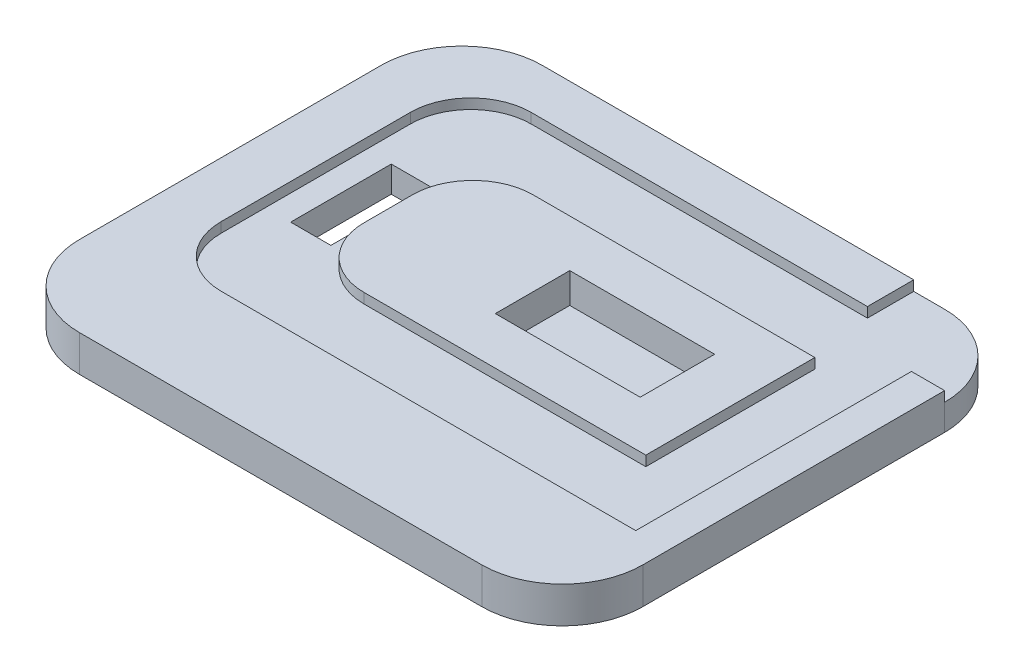
SolidWorks part; units mm, degrees
ref_plane "Front" through (0, 0, 0) normal (0, 0, 1) x (1, 0, 0)
ref_plane "Top" through (0, 0, 0) normal (0, 1, 0) x (1, 0, 0)
ref_plane "Right" through (0, 0, 0) normal (1, 0, 0) x (0, 0, -1)
sketch "Sketch2" plane through (0, 0, 0) normal (0, 1, 0) x (1, 0, 0)
  line L1 (-80, 50) -> (60, 50)
  line L2 (-80, 50) -> (-80, -65)
  line L3 (-80, -65) -> (60, -65)
  line L4 (60, 50) -> (60, -65)
  dimension "D1" = 140
  dimension "D2" = 115
  dimension "D3" = 65
  dimension "D4" = 80
extrude "Boss-Extrude1" add sketch "Sketch2" against normal blind 9 contours L3 L4 L1 L2
sketch "Sketch3" plane through (0, 0, 0) normal (0, 1, 0) x (1, 0, 0)
  line L1 (-60, 12.5) -> (-50, 12.5)
  line L2 (-60, 12.5) -> (-60, -12.5)
  line L3 (-60, -12.5) -> (-50, -12.5)
  line L4 (-50, 12.5) -> (-50, -12.5)
  line L5 (-51, -17.5) -> (-63, -17.5) construction
  line L7 (-65, 22.5) -> (-65, -22.5) construction
  dimension "D1" = 25
  dimension "D2" = 10
  dimension "D3" = 5
  dimension "D4" = 5
extrude "Cut-Extrude1" cut sketch "Sketch3" against normal through all
fillet "Fillet1" radius 20 4 edges at (60, -4.5, -50) (-80, -4.5, -50) (-80, -4.5, 65) (60, -4.5, 65)
ref_plane "Plane1" through (0, 0, 20) normal (0, 0, 1) x (1, 0, 0)
sketch "Sketch6" plane through (0, 0, 0) normal (0, 1, 0) x (1, 0, 0)
  line L0 (60, 30) -> (60, -45) construction
  line L1 (-66.25, 38.5) -> (51.75, 38.5)
  line L2 (-66.25, 38.5) -> (-66.25, -38.5)
  line L3 (-66.25, -38.5) -> (51.75, -38.5)
  line L4 (51.75, 38.5) -> (51.75, 21)
  line L5 (-60, 50) -> (40, 50) construction
  line L6 (51.75, 21) -> (51.75, -38.5)
  line L7 (36.75, 21) -> (-48.25, 21)
  line L9 (36.75, -21) -> (-48.25, -21)
  line L10 (-48.25, 21) -> (-48.25, -21)
  line L15 (36.75, 21) -> (36.75, -21)
  point P12 (-48.25, 0)
  point P13 (-66.25, 0)
  dimension "D1" = 118
  dimension "D2" = 8.25
  dimension "D3" = 11.5
  dimension "D4" = 77
  dimension "D5" = 100
  dimension "D6" = 42
  dimension "D7" = 15
extrude "Cut-Extrude4" cut sketch "Sketch6" against normal blind 2.5
sketch "Sketch7" plane through (0, 0, 0) normal (0, 1, 0) x (1, 0, 0)
  line L0 (23.1, 8.75) -> (23.1, -8.75) construction
  line L1 (-12.4, 9.25) -> (23.6, 9.25)
  line L2 (-12.4, 9.25) -> (-12.4, -9.25)
  line L3 (-12.4, -9.25) -> (23.6, -9.25)
  line L4 (23.6, 9.25) -> (23.6, -9.25)
  line L5 (-11.9, -8.75) -> (23.1, -8.75) construction
  line L6 (-11.9, 8.75) -> (-11.9, -8.75) construction
  line L7 (-11.9, 8.75) -> (23.1, 8.75) construction
  dimension "D1" = 0.5
  dimension "D2" = 0.5
  dimension "D3" = 0.5
  dimension "D4" = 0.5
extrude "Cut-Extrude5" cut sketch "Sketch7" against normal blind 7.5
fillet "Fillet2" radius 15 4 edges at (-66.25, -1.25, 38.5) (-66.25, -1.25, -38.5) (-48.25, -1.25, -21) (-48.25, -1.25, 21)
sketch "Sketch8" plane through (0, 0, 0) normal (0, 1, 0) x (1, 0, 0)
  line L0 (-60, 50) -> (40, 50) construction
  line L1 (32.3133, 50) -> (60, 50)
  line L2 (32.3133, 50) -> (32.3133, 30)
  line L3 (32.3133, 30) -> (60, 30)
  line L4 (60, 50) -> (60, 30)
  line L5 (60, 30) -> (60, -45) construction
  arc A0 (60, 30) -> (40, 50) centre (40, 30) ccw construction
extrude "Cut-Extrude6" cut sketch "Sketch8" against normal blind 2.5
